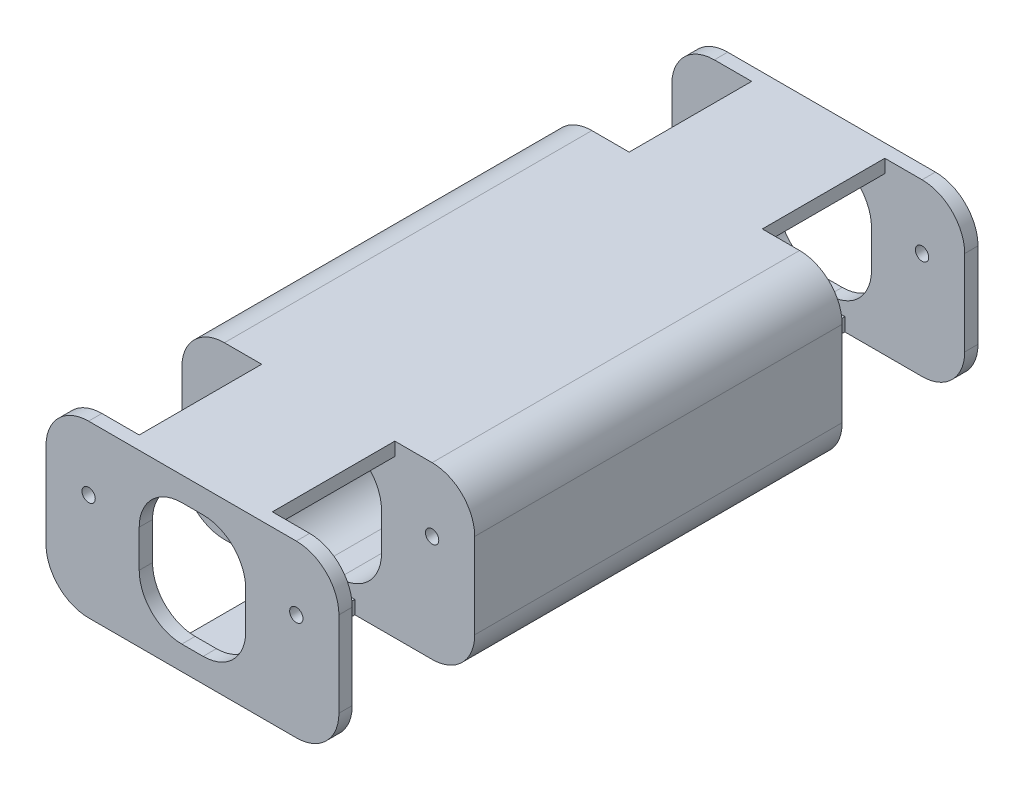
SolidWorks part; units mm, degrees
material "ABS"
ref_plane "Front Plane" through (0, 0, 0) normal (0, 0, 1) x (1, 0, 0)
ref_plane "Top Plane" through (0, 0, 0) normal (0, 1, 0) x (1, 0, 0)
ref_plane "Right Plane" through (0, 0, 0) normal (1, 0, 0) x (0, 0, -1)
sketch "Sketch1" plane through (0, 0, 0) normal (0, 0, 1) x (1, 0, 0)
  line L0 (0, -50) -> (0, 50) construction
  line L1 (-55, -32) -> (55, -32)
  line L2 (-55, -32) -> (-55, 32)
  line L3 (-55, 32) -> (55, 32)
  line L4 (55, -32) -> (55, 32)
  line L5 (-55, -32) -> (55, 32) construction
  line L6 (-55, 32) -> (55, -32) construction
  line L7 (-39, 0) -> (39, 0) construction
  line L8 (39, 0) -> (39, 8) construction
  line L9 (-39, 0) -> (-39, 8) construction
  line L11 (-20, -23) -> (20, -23)
  line L12 (-20, -23) -> (-20, 23)
  line L13 (-20, 23) -> (20, 23)
  line L14 (20, -23) -> (20, 23)
  line L15 (-20, -23) -> (20, 23) construction
  line L16 (-20, 23) -> (20, -23) construction
  circle A0 centre (39, 8) radius 2.5
  circle A1 centre (-39, 8) radius 2.5
  point P0 (0, 0)
  point P9 (0, 0)
  point P12 (0, 0)
  point P17 (0, 0)
  dimension "D6" = 5
  dimension "D7" = 5
  dimension "D1" = 64
  dimension "D2" = 110
  dimension "D3" = 8
  dimension "D4" = 78
  dimension "D5" = 8
  dimension "D8" = 46
  dimension "D9" = 40
extrude "Boss-Extrude1" add sketch "Sketch1" along normal blind 5
fillet "Fillet1" radius 16 4 edges at (-55, -32, 2.5) (55, -32, 2.5) (55, 32, 2.5) (-55, 32, 2.5)
fillet "Fillet2" radius 16 4 edges at (-20, 23, 2.5) (20, 23, 2.5) (20, -23, 2.5) (-20, -23, 2.5)
sketch "Sketch2" plane through (0, 0, 5) normal (0, 0, 1) x (1, 0, 0)
  line L0 (0, 32) -> (0, -32) construction
  line L1 (39, 32) -> (-39, 32) construction
  line L2 (-39, -32) -> (39, -32) construction
  line L3 (-25, 27) -> (-25, 32)
  line L4 (-25, 27) -> (25, 27)
  line L5 (-25, 32) -> (25, 32)
  line L6 (25, 27) -> (25, 32)
  line L7 (-25, 27) -> (25, 32) construction
  line L8 (-25, 32) -> (25, 27) construction
  line L10 (-10, -27) -> (10, -27)
  line L11 (-10, -27) -> (-10, -32)
  line L12 (-10, -32) -> (10, -32)
  line L13 (10, -27) -> (10, -32)
  line L14 (-10, -27) -> (10, -32) construction
  line L15 (-10, -32) -> (10, -27) construction
  point P6 (25, 29.5)
  point P7 (0, 29.5)
  point P9 (0, -29.5)
  dimension "D1" = 2.5
  dimension "D2" = 50
  dimension "D3" = 20
  dimension "D4" = 5
extrude "Boss-Extrude2" add sketch "Sketch2" along normal blind 46
extrude "Boss-Extrude3" add sketch "Sketch1<2>" along normal offset from surface (69 mm away) 69 from surface up to face at (0, 29.5, 51) offset beyond the face yes starting at face at (0, 29.5, 51)
sketch "Sketch1<2>" plane through (0, 0, 0) normal (0, 0, 1) x (1, 0, 0) same geometry as "Sketch1"
fillet "Fillet3" radius 16 8 edges at (-55, -32, 85.5) (55, -32, 85.5) (20, -23, 85.5) (-20, 23, 85.5) (-20, -23, 85.5) (20, 23, 85.5) (55, 32, 85.5) (-55, 32, 85.5)
ref_plane "Plane1" through (0, 0, 120) normal (0, 0, 1) x (1, 0, 0)
mirror "Mirror2" about plane through (0, 0, 120) normal (0, 0, 1) of "Boss-Extrude1", "Fillet1", "Fillet2", "Boss-Extrude2", "Boss-Extrude3", "Fillet3"
